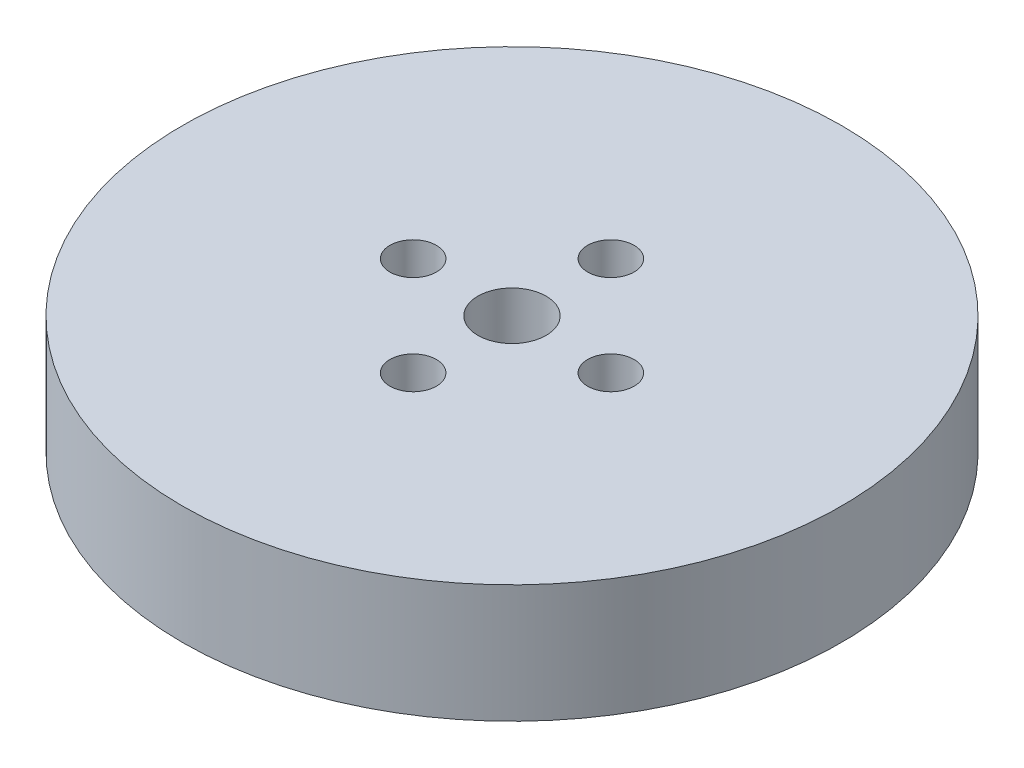
SolidWorks part; units mm, degrees
ref_plane "Front Plane" through (0, 0, 0) normal (0, 0, 1) x (1, 0, 0)
ref_plane "Top Plane" through (0, 0, 0) normal (0, 1, 0) x (1, 0, 0)
ref_plane "Right Plane" through (0, 0, 0) normal (1, 0, 0) x (0, 0, -1)
sketch "Sketch1" plane through (0, 0, 0) normal (0, 1, 0) x (1, 0, 0)
  circle A0 centre (0, 0) radius 72.5
  dimension "FLANGE_OD" = 145
extrude "Boss-Extrude1" add sketch "Sketch1" along normal blind 26
sketch "Sketch2" plane through (0, 0, 0) normal (0, 1, 0) x (1, 0, 0)
  circle A0 centre (0, 0) radius 7.5
  dimension "BORE_D" = 15
extrude "Cut-Extrude1" cut sketch "Sketch2" along normal through all
sketch "Sketch3" plane through (0, 26, 0) normal (0, 1, 0) x (1, 0, 0)
  circle A0 centre (0, 0) radius 21.7488 construction
  circle A1 centre (-21.7488, 0) radius 5.1065
  dimension "BOLT_D" = 10.2131
  dimension "BOLT_PCD" = 43.4976
extrude "Cut-Extrude2" cut sketch "Sketch3" against normal blind 21.6631
pattern_circular "CirPattern1" count 4 over 360 about axis through (0, 0, 0) along (0, 1, 0) of "Cut-Extrude2"
